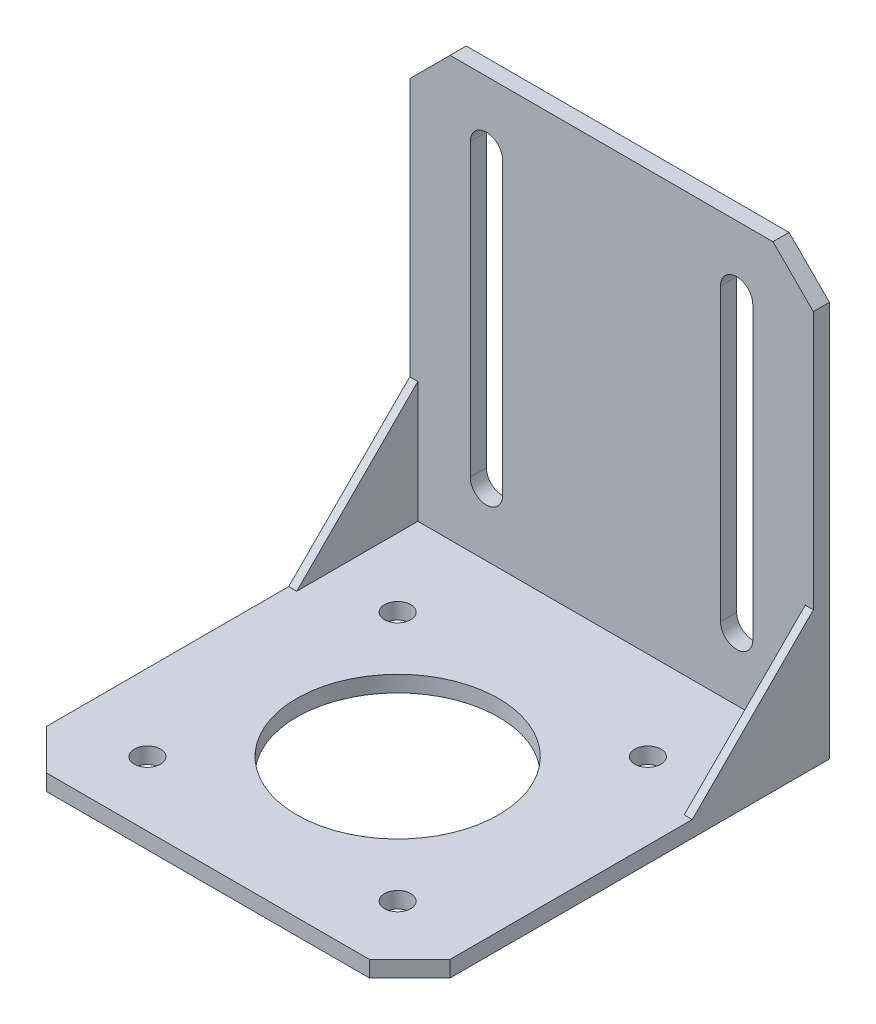
SolidWorks part; units mm, degrees
ref_plane "Front Plane" through (0, 0, 0) normal (0, 0, 1) x (1, 0, 0)
ref_plane "Top Plane" through (0, 0, 0) normal (0, 1, 0) x (1, 0, 0)
ref_plane "Right Plane" through (0, 0, 0) normal (1, 0, 0) x (0, 0, -1)
sketch "Sketch1" plane through (0, 0, 0) normal (1, 0, 0) x (0, 0, -1)
  line L0 (-26, 0) -> (26, 0)
  line L1 (26, 0) -> (26, 54)
  line L2 (-26, 2) -> (24, 2)
  line L3 (24, 2) -> (24, 54)
  line L4 (-26, 0) -> (-26, 2)
  line L5 (26, 54) -> (24, 54)
  dimension "D1" = 54
  dimension "D2" = 52
  dimension "D3" = 2
extrude "Boss-Extrude1" add sketch "Sketch1" against normal blind 50
chamfer "Chamfer1" distance 5 angle 45 4 edges at (0, 1, 26) (-50, 54, -25) (0, 54, -25) (-50, 1, 26)
sketch "Sketch2" plane through (0, 2, 0) normal (0, 1, 0) x (1, 0, 0)
  line L0 (-45, -26) -> (-5, -26) construction
  line L1 (-40.5, 13) -> (-40.5, -18) construction
  line L2 (-40.5, -2.5) -> (-9.5, -2.5) construction
  line L3 (-50, 24) -> (-50, -21) construction
  circle A0 centre (-40.5, 13) radius 1.625
  circle A1 centre (-9.5, 13) radius 1.625
  circle A2 centre (-9.5, -18) radius 1.625
  circle A3 centre (-40.5, -18) radius 1.625
  circle A4 centre (-25, -2.5) radius 12.5
  dimension "D1" = 3.25
  dimension "D4" = 25
  dimension "D6" = 15.5
  dimension "D2" = 31
  dimension "D3" = 31
  dimension "D5" = 8
  dimension "D7" = 9.5
extrude "Cut-Extrude1" cut sketch "Sketch2" against normal through all
sketch "Sketch3" plane through (0, 0, -24) normal (0, 0, 1) x (1, 0, 0)
  line L0 (-25, 2) -> (-25, 54) construction
  line L1 (-45, 2) -> (-5, 2) construction
  line L2 (-45, 54) -> (-5, 54) construction
  line L3 (-40.5, 46) -> (-40.5, 10) construction
  line L4 (-38.5, 46) -> (-38.5, 10)
  line L5 (-42.5, 46) -> (-42.5, 10)
  line L6 (-9.5, 46) -> (-9.5, 10) construction
  line L7 (-11.5, 46) -> (-11.5, 10)
  line L8 (-7.5, 46) -> (-7.5, 10)
  line L9 (-50, 2) -> (0, 2) construction
  line L10 (0, 49) -> (0, 2) construction
  arc A0 (-38.5, 46) -> (-42.5, 46) centre (-40.5, 46) ccw
  arc A1 (-42.5, 10) -> (-38.5, 10) centre (-40.5, 10) ccw
  arc A2 (-11.5, 46) -> (-7.5, 46) centre (-9.5, 46) cw
  arc A3 (-7.5, 10) -> (-11.5, 10) centre (-9.5, 10) cw
  point P8 (-40.5, 28)
  point P13 (0, 0)
  point P16 (-9.5, 28)
  dimension "D3" = 2
  dimension "D1" = 8
  dimension "D2" = 8
  dimension "D4" = 9.5
extrude "Cut-Extrude2" cut sketch "Sketch3" against normal through all
sketch "Sketch4" plane through (0, 0, 0) normal (1, 0, 0) x (0, 0, -1)
  line L2 (24, 2) -> (-21, 2) construction
  line L3 (9, 2) -> (24, 2)
  line L4 (24, 2) -> (24, 17)
  line L5 (24, 49) -> (24, 2) construction
  line L6 (24, 17) -> (9, 2)
  dimension "D1" = 15
  dimension "D2" = 15
extrude "Boss-Extrude2" add sketch "Sketch4" against normal blind 1
extrude "Boss-Extrude3" add sketch "Sketch4<2>" along normal blind 1 from surface starting at face at (-50, 17, -9.6667)
sketch "Sketch4<2>" plane through (0, 0, 0) normal (1, 0, 0) x (0, 0, -1) same geometry as "Sketch4"
